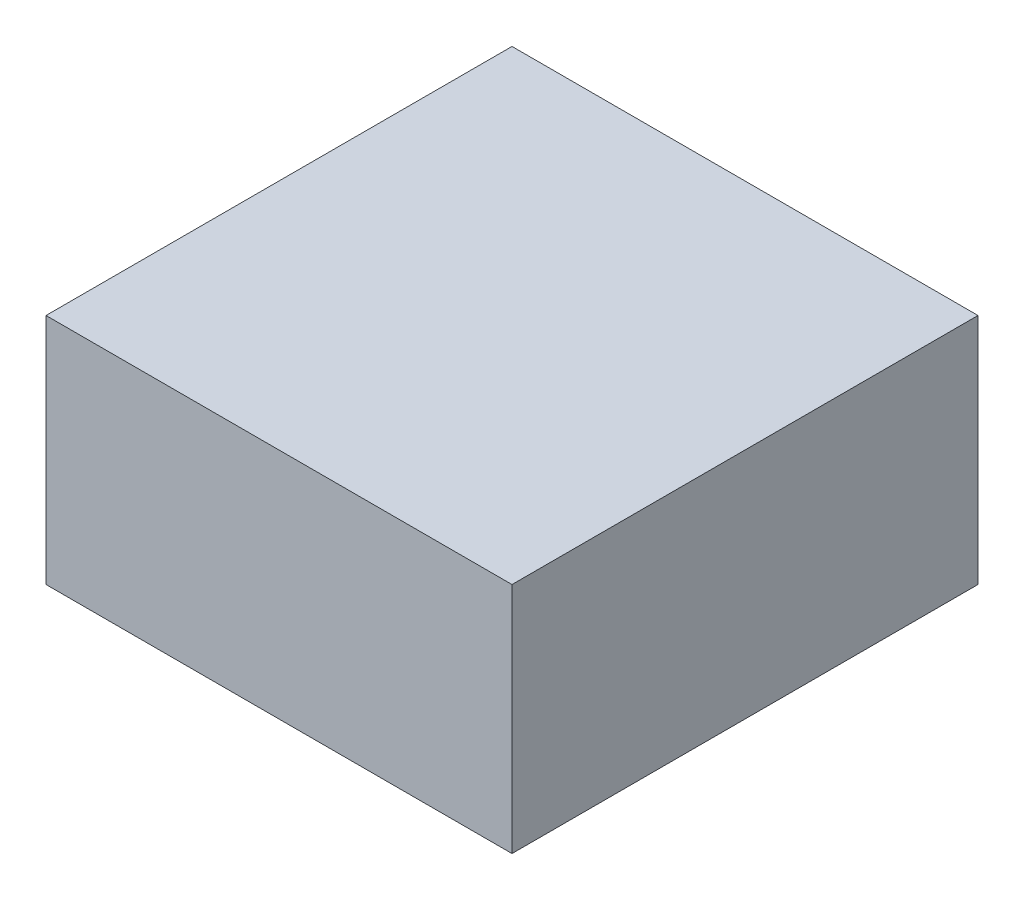
SolidWorks part; units mm, degrees
ref_plane "Front Plane" through (0, 0, 0) normal (0, 0, 1) x (1, 0, 0)
ref_plane "Top Plane" through (0, 0, 0) normal (0, 1, 0) x (1, 0, 0)
ref_plane "Right Plane" through (0, 0, 0) normal (1, 0, 0) x (0, 0, -1)
sketch "Sketch1" plane through (0, 0, 0) normal (0, 1, 0) x (1, 0, 0)
  line L1 (5, -5) -> (-5, -5)
  line L2 (5, -5) -> (5, 5)
  line L3 (5, 5) -> (-5, 5)
  line L4 (-5, -5) -> (-5, 5)
  line L5 (5, -5) -> (-5, 5) construction
  line L6 (5, 5) -> (-5, -5) construction
  point P0 (0, 0)
  dimension "D1" = 10
  dimension "D2" = 10
extrude "Boss-Extrude1" add sketch "Sketch1" along normal blind 5
